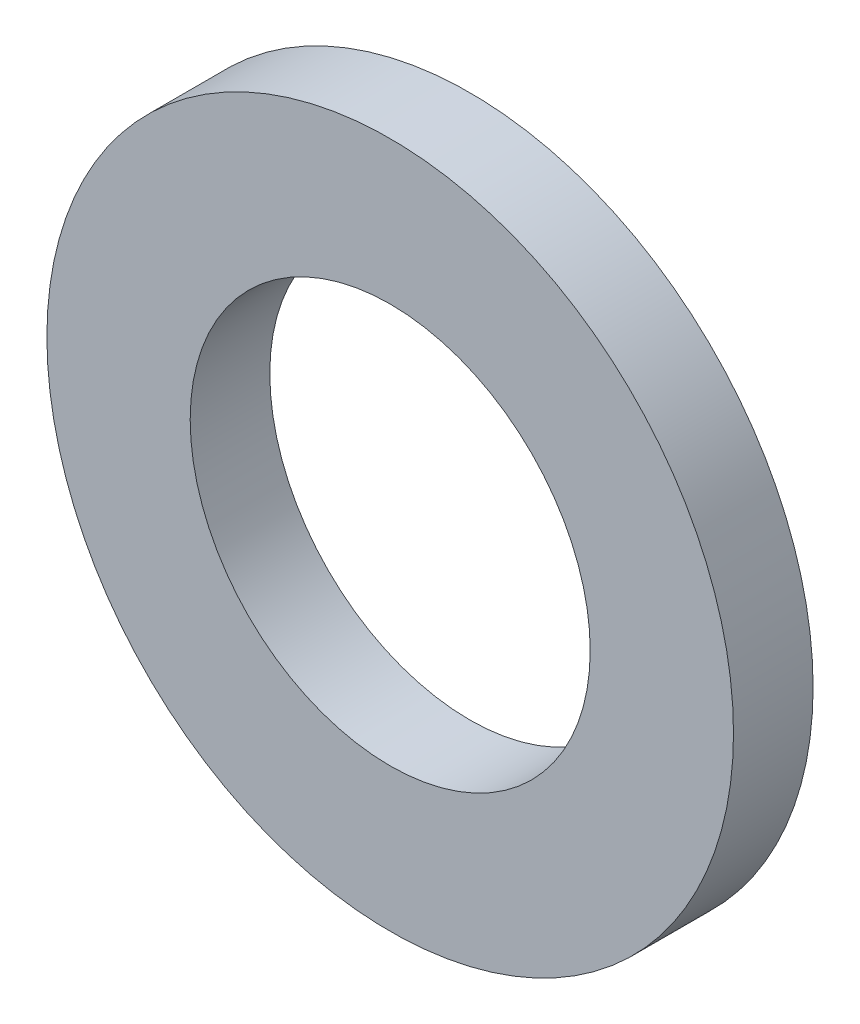
SolidWorks part; units mm, degrees
material "1060 Alloy"
ref_plane "Front Plane" through (0, 0, 0) normal (0, 0, 1) x (1, 0, 0)
ref_plane "Top Plane" through (0, 0, 0) normal (0, 1, 0) x (1, 0, 0)
ref_plane "Right Plane" through (0, 0, 0) normal (1, 0, 0) x (0, 0, -1)
sketch "Sketch1" plane through (0, 0, 0) normal (0, 0, 1) x (1, 0, 0)
  circle A0 centre (0, 0) radius 17.25
  circle A1 centre (0, 0) radius 10.05
  dimension "D1" = 20.1
  dimension "D2" = 34.5
extrude "Boss-Extrude1" add sketch "Sketch1" along normal blind 4
